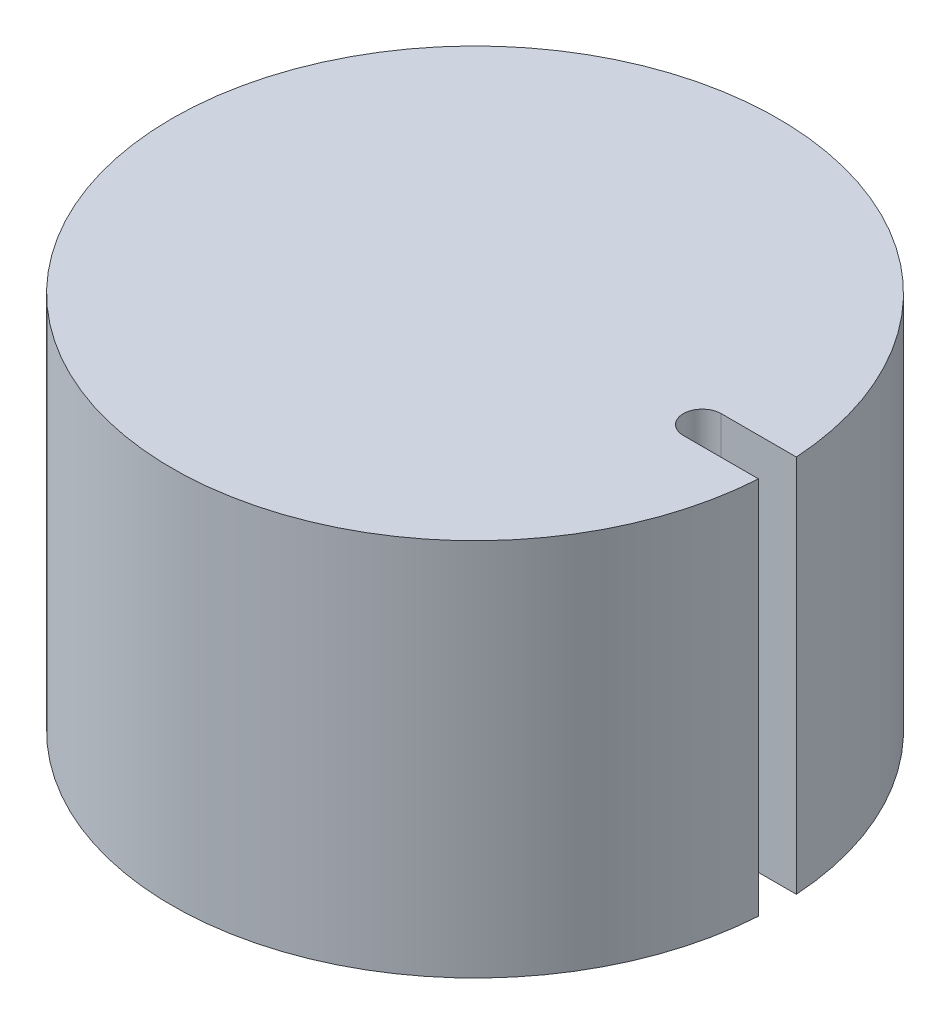
SolidWorks part; units mm, degrees
ref_plane "前视基准面" through (0, 0, 0) normal (0, 0, 1) x (1, 0, 0)
ref_plane "上视基准面" through (0, 0, 0) normal (0, 1, 0) x (1, 0, 0)
ref_plane "右视基准面" through (0, 0, 0) normal (1, 0, 0) x (0, 0, -1)
other "Configuration Table"
sketch "草图1" plane through (0, 0, 0) normal (0, 1, 0) x (1, 0, 0)
  circle A0 centre (0, 0) radius 40
  point P3 (0, 0)
  dimension "D1" = 80
extrude "凸台-拉伸1" add sketch "草图1" along normal blind 50
sketch "草图2" plane through (0, 0, 0) normal (0, -1, 0) x (1, 0, 0)
  line L1 (18.5405, 7.5) -> (25, 7.5)
  line L3 (18.5405, -7.5) -> (25, -7.5)
  line L4 (25, 7.5) -> (25, -7.5)
  line L5 (20, 0) -> (25, -7.5) construction
  line L6 (20, 0) -> (25, 7.5) construction
  arc A0 (18.5405, 7.5) -> (18.5405, -7.5) centre (0, 0) ccw
  point P3 (20, 0)
  dimension "D1" = 40
  dimension "D2" = 15
  dimension "D3" = 5
  dimension "D4" = 6.4595
extrude "切除-拉伸1" cut sketch "草图2" against normal blind 30
ref_axis "基准轴1" through (0, 92.7749, 0) along (0, -1, 0)
sketch "草图4" plane through (0, 0, 0) normal (0, -1, 0) x (1, 0, 0)
  line L0 (40, 0) -> (30, 0) construction
  line L1 (40, -2.5) -> (30, -2.5)
  line L2 (40, 2.5) -> (30, 2.5)
  circle A0 centre (0, 0) radius 40 construction
  arc A1 (40, -2.5) -> (40, 2.5) centre (40, 0) ccw
  arc A2 (30, 2.5) -> (30, -2.5) centre (30, 0) ccw
  point P6 (35, 0)
  dimension "D1" = 10
  dimension "D2" = 5
extrude "切除-拉伸2" cut sketch "草图4" against normal through all
